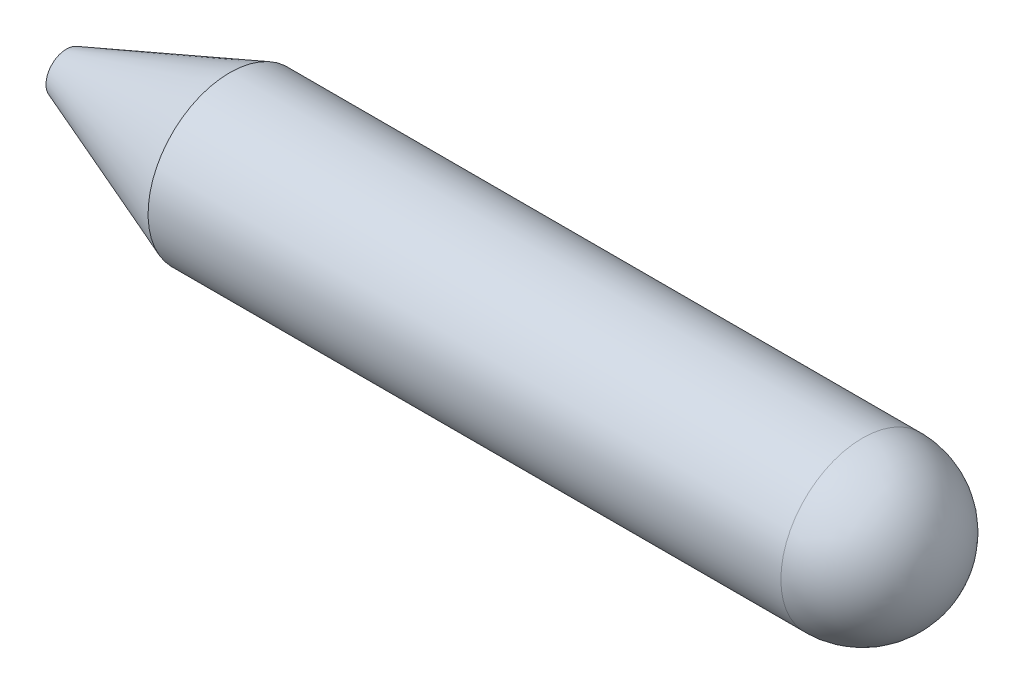
SolidWorks part; units mm, degrees
ref_plane "Plan de face" through (0, 0, 0) normal (0, 0, 1) x (1, 0, 0)
ref_plane "Plan de dessus" through (0, 0, 0) normal (0, 1, 0) x (1, 0, 0)
ref_plane "Plan de droite" through (0, 0, 0) normal (1, 0, 0) x (0, 0, -1)
sketch "Sketch2" plane through (0, 0, 0) normal (0, 0, 1) x (1, 0, 0)
  line L0 (-21.5, 0) -> (-21.5, 0.5)
  line L1 (0, 0) -> (-21.5, 0)
  line L3 (-2, 2) -> (-17.5, 2)
  line L5 (-21.5, 0.5) -> (-17.5, 2)
  arc A0 (0, 0) -> (-2, 2) centre (-2, 0) ccw
  point P2 (0, 0)
  dimension "D5" = 2
  dimension "D1" = 15.5
  dimension "D2" = 21.5
  dimension "D3" = 0.5
  dimension "D4" = 2
  dimension "D6" = 4
revolve "Revolve1" add sketch "Sketch2" angle 360 about L1
